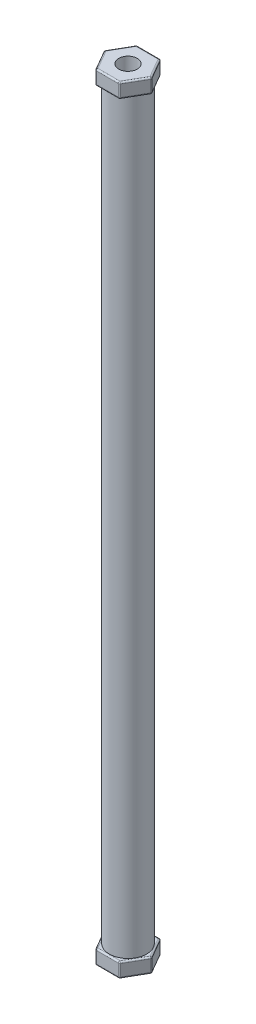
SolidWorks part; units mm, degrees
ref_plane "Front Plane" through (0, 0, 0) normal (0, 0, 1) x (1, 0, 0)
ref_plane "Top Plane" through (0, 0, 0) normal (0, 1, 0) x (1, 0, 0)
ref_plane "Right Plane" through (0, 0, 0) normal (1, 0, 0) x (0, 0, -1)
sketch "Sketch1" plane through (0, 0, 0) normal (0, 1, 0) x (1, 0, 0)
  circle A0 centre (0, 0) radius 6.35
  circle A1 centre (0, 0) radius 3.175
  dimension "D1" = 12.7
extrude "Boss-Extrude1" add sketch "Sketch1" along normal blind 254
ref_plane "Plane1" through (0, 127, 0) normal (0, 1, 0) x (1, 0, 0)
sketch "Sketch2" plane through (0, 254, 0) normal (0, 1, 0) x (1, 0, 0)
  line L1 (-8.0656, 0) -> (-4.0328, -6.985)
  line L2 (-4.0328, -6.985) -> (4.0328, -6.985)
  line L3 (4.0328, -6.985) -> (8.0656, 0)
  line L4 (8.0656, 0) -> (4.0328, 6.985)
  line L5 (4.0328, 6.985) -> (-4.0328, 6.985)
  line L6 (-4.0328, 6.985) -> (-8.0656, 0)
  circle A0 centre (0, 0) radius 6.985 construction
  circle A1 centre (0, 0) radius 3.175
  dimension "D1" = 13.97
extrude "Boss-Extrude2" add sketch "Sketch2" along normal blind 5
fillet "Fillet1" radius 0.5 18 edges at (6.0492, 254, -3.4925) (4.0328, 256.5, -6.985) (8.0656, 256.5, 0) (-4.0328, 256.5, -6.985) (-6.0492, 254, -3.4925) (-8.0656, 256.5, 0) (-6.0492, 254, 3.4925) (-4.0328, 256.5, 6.985) (0, 254, 6.985) (6.0492, 254, 3.4925) (4.0328, 256.5, 6.985) (6.0492, 259, 3.4925) (6.0492, 259, -3.4925) (0, 259, -6.985) (-6.0492, 259, -3.4925) (-6.0492, 259, 3.4925) (0, 259, 6.985) (0, 254, -6.985)
mirror "Mirror1" about plane through (0, 127, 0) normal (0, 1, 0) of "Fillet1", "Boss-Extrude2"
